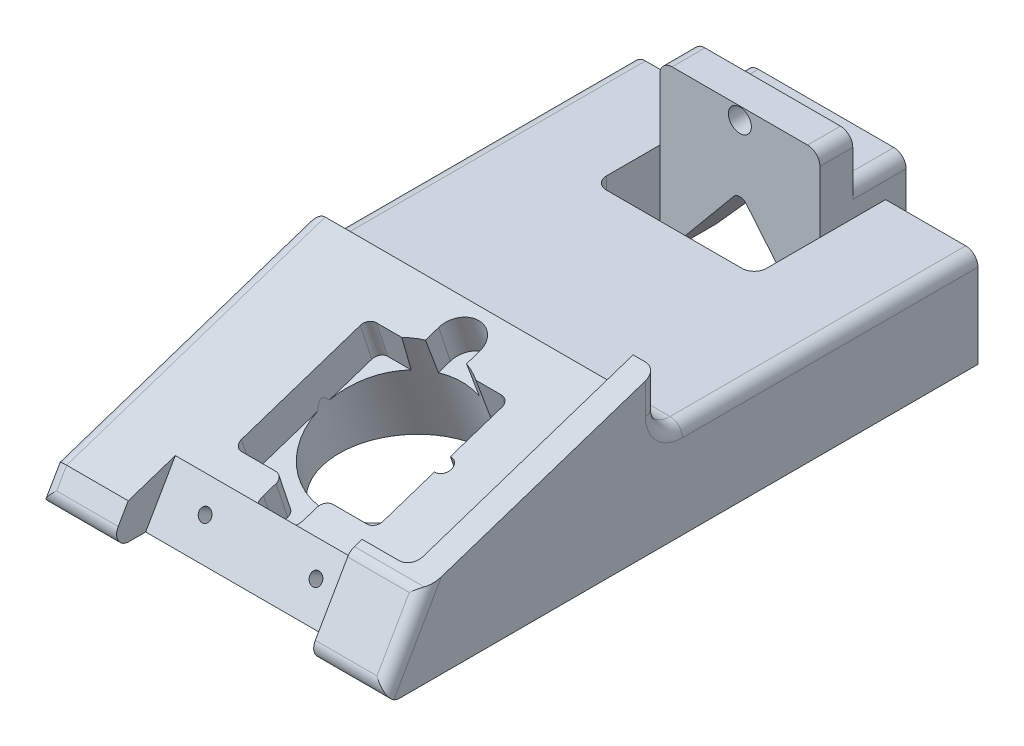
SolidWorks part; units mm, degrees
ref_plane "前视基准面" through (0, 0, 0) normal (0, 0, 1) x (1, 0, 0)
ref_plane "上视基准面" through (0, 0, 0) normal (0, 1, 0) x (1, 0, 0)
ref_plane "右视基准面" through (0, 0, 0) normal (1, 0, 0) x (0, 0, -1)
sketch "草图1" plane through (0, 0, 0) normal (0, 1, 0) x (1, 0, 0)
  line L1 (-21, 36.5) -> (21, 36.5)
  line L2 (-21, 36.5) -> (-21, -36.5)
  line L3 (-21, -36.5) -> (21, -36.5)
  line L4 (21, 36.5) -> (21, -36.5)
  line L5 (-21, 36.5) -> (21, -36.5) construction
  line L6 (-21, -36.5) -> (21, 36.5) construction
  point P0 (0, 0)
  dimension "D1" = 73
  dimension "D2" = 42
extrude "凸台-拉伸1" add sketch "草图1" along normal blind 19
sketch "草图3" plane through (-21, 0, 0) normal (-1, 0, 0) x (0, 0, 1)
  line L0 (-36.5, 11.75) -> (2.5, 11.75)
  line L1 (-36.5, 19) -> (-36.5, 0) construction
  line L2 (-36.5, 0) -> (36.5, 0) construction
  line L3 (2.5, 11.75) -> (2.5, 19)
  line L4 (-36.5, 19) -> (36.5, 19) construction
  line L5 (2.5, 19) -> (30.9777, 9.5649)
  line L6 (30.9777, 9.5649) -> (36.5, 0)
  line L7 (-36.5, 11.75) -> (-36.5, 19)
  line L8 (-36.5, 19) -> (2.5, 19)
  line L9 (36.5, 19) -> (36.5, 0)
  line M5 (36.5, 0) -> (36.5, 19)
  line M6 (36.5, 19) -> (-36.5, 19)
  line M7 (-36.5, 19) -> (-36.5, 0)
  dimension "D1" = 11.75
  dimension "D2" = 39
  dimension "D3" = 60
  dimension "D4" = 30
extrude "切除-拉伸1" cut sketch "草图3" against normal up to next contours L0 L3 M6 M7 | L5 L6 M5 M6
sketch "草图4" plane through (0, 11.75, 0) normal (0, 1, 0) x (1, 0, 0)
  line L0 (21, 36.5) -> (-21, 36.5) construction
  line L2 (-9.75, 28.5) -> (9.75, 28.5)
  line L3 (9.75, 28.5) -> (9.75, 22)
  line L4 (8.25, 20.5) -> (-8.25, 20.5)
  line L5 (-9.75, 22) -> (-9.75, 28.5)
  line L6 (21, -2.5) -> (21, 36.5) construction
  line L7 (-21, 36.5) -> (-21, -2.5) construction
  arc A0 (9.75, 22) -> (8.25, 20.5) centre (8.25, 22) cw
  arc A1 (-8.25, 20.5) -> (-9.75, 22) centre (-8.25, 22) cw
  point P5 (-0.2557, 36.5)
  point P11 (9.75, 20.5)
  dimension "D4" = 1.5
  dimension "D1" = 8
  dimension "D3" = 8
  dimension "D5" = 11.25
  dimension "D6" = 19.5
  dimension "D7" = 11.25
  dimension "D8" = 42
extrude "切除-拉伸2" cut sketch "草图4" against normal blind 19 contours A1 L4 A0 L3 L2 L5
sketch "草图5" plane through (0, 11.75, 0) normal (0, 1, 0) x (1, 0, 0)
  line L0 (9.75, 28.5) -> (9.75, 32.5)
  line L1 (9.75, 32.5) -> (-9.75, 32.5)
  line L2 (-9.75, 32.5) -> (-9.75, 28.5)
  line L7 (-9.75, 28.5) -> (-9.75, 22)
  line L8 (9.75, 28.5) -> (-9.75, 28.5)
  line L9 (9.75, 22) -> (9.75, 28.5)
  line L10 (-8.25, 20.5) -> (8.25, 20.5)
  line L12 (9.75, 28.5) -> (-9.75, 28.5)
  arc A2 (-9.75, 22) -> (-8.25, 20.5) centre (-8.25, 22) ccw
  arc A3 (8.25, 20.5) -> (9.75, 22) centre (8.25, 22) ccw
  dimension "D1" = 4
  dimension "D2" = 0
extrude "凸台-拉伸2" add sketch "草图5" along normal blind 9
sketch "草图6" plane through (0, 11.75, 0) normal (0, 1, 0) x (1, 0, 0)
  line L0 (-9.75, 32.5) -> (-9.75, 39)
  line L1 (-9.75, 39) -> (9.75, 39)
  line L2 (9.75, 39) -> (9.75, 32.5)
  line L3 (9.75, 32.5) -> (-9.75, 32.5)
  dimension "D1" = 6.5
extrude "凸台-拉伸3" add sketch "草图6" against normal up to surface (11.75 mm away) and the other way blind 3.5 up to face at (0, 0, 0)
sketch "草图7" plane through (0, 0, -39) normal (0, 0, -1) x (-1, 0, 0)
  line L0 (-21, 11.75) -> (21, 11.75) construction
  line L1 (-21, 11.75) -> (21, 11.75)
  line L2 (0, 11.75) -> (-9.75, 0)
  line L3 (0, 11.75) -> (9.75, 0)
  line L4 (9.75, 0) -> (-9.75, 0)
  line M2 (-9.75, 0) -> (9.75, 0)
extrude "切除-拉伸3" cut sketch "草图7" against normal up to next contours L3 L2 M2
fillet "圆角1" radius 1.5 4 edges at (-9.75, 15.25, -35.75) (9.75, 15.25, -35.75) (-9.75, 20.75, -30.5) (9.75, 20.75, -30.5)
fillet "圆角2" radius 1 1 edges at (0, 11.75, -33.75)
sketch "草图8" plane through (9.75, 0, 0) normal (1, 0, 0) x (0, 0, -1)
  line L0 (36.5, 0) -> (39, 4)
  line L1 (39, 13.75) -> (39, 0) construction
  line L2 (39, 4) -> (39, 0)
  line L3 (39, 0) -> (36.5, 0)
  dimension "D1" = 4
extrude "切除-拉伸4" cut sketch "草图8" against normal blind 20
fillet "圆角3" radius 1.5 2 edges at (-8.0904, 2, -37.75) (8.0904, 2, -37.75)
sketch "草图9" plane through (0, 17.867, 5.9196) normal (0, 0.9493, 0.3145) x (1, 0, 0)
  line L0 (-18, -24.8476) -> (-21, -24.8476)
  line L1 (-18, 3.6024) -> (18, 3.6024)
  line L2 (-18, 3.6024) -> (-18, -24.8476)
  line L3 (-18, -24.8476) -> (18, -24.8476)
  line L4 (21, -26.3976) -> (21, 3.6024)
  line L5 (21, 3.6024) -> (-21, 3.6024)
  line L6 (-21, 3.6024) -> (-21, -26.3976)
  line L7 (-21, -26.3976) -> (21, -26.3976)
  line L8 (21, -26.3976) -> (21, 3.6024)
  line L9 (21, 3.6024) -> (-21, 3.6024)
  line L10 (-21, 3.6024) -> (-21, -26.3976)
  line L11 (-21, -26.3976) -> (21, -26.3976)
  line L12 (18, 3.6024) -> (18, -24.8476)
  line L13 (-18, 3.6024) -> (18, -24.8476) construction
  line L14 (-18, -24.8476) -> (18, 3.6024) construction
  line L15 (-18, -24.8476) -> (-18, -26.3976)
  point P2 (0, -10.6226)
  line M10 (21, 3.6024) -> (-21, 3.6024)
  line M11 (-21, 3.6024) -> (-21, -26.3976)
  dimension "D2" = 3
  dimension "D3" = 0
  dimension "D4" = 3
  dimension "D5" = 1.55
  dimension "D1" = 0
extrude "切除-拉伸5" cut sketch "草图9" against normal blind 4 contours L12 L2 L3 M10 | L2 L0 M10 M11
sketch "草图10" plane through (0, 15.805, 27.375) normal (0, 0.5, 0.866) x (1, 0, 0)
  line L0 (-12, -18.25) -> (-12, -7.2054)
  line L1 (12, -18.25) -> (12, -7.2054)
  line L2 (-21, -6.0475) -> (18, -6.0475) construction
  line L3 (-21, -6.0475) -> (18, -6.0475)
  line L4 (21, -18.25) -> (21, -7.2054)
  line L5 (21, -7.2054) -> (-21, -7.2054)
  line L6 (-21, -7.2054) -> (-21, -18.25)
  line L7 (-21, -18.25) -> (21, -18.25)
  line L8 (21, -18.25) -> (21, -7.2054)
  line L9 (21, -7.2054) -> (-21, -7.2054)
  line L10 (-21, -7.2054) -> (-21, -18.25)
  line L11 (-21, -18.25) -> (21, -18.25)
  line L12 (-12, -7.2054) -> (-12, -6.0475)
  line L13 (12, -7.2054) -> (12, -6.0475)
  line L14 (12, -6.0475) -> (-12, -6.0475)
  line M8 (21, -7.2054) -> (-21, -7.2054)
  line M10 (-21, -18.25) -> (21, -18.25)
  dimension "D2" = 9
  dimension "D3" = 9
  dimension "D1" = 0
extrude "切除-拉伸7" cut sketch "草图10" against normal up to vertex (12.8767 mm away) contours L1 L0 M10 M8 | L13 L3 L12 M8
sketch "草图12" plane through (0, 14.07, 4.6616) normal (0, 0.9493, 0.3145) x (1, 0, 0)
  line L0 (-17.249, 2.2772) -> (18, -24.8476) construction
  line L6 (18, 2.2772) -> (-21, 2.2772)
  line L7 (-21, 2.2772) -> (-21, -24.8476)
  line L8 (-21, -24.8476) -> (-12, -24.8476)
  line L9 (-12, -24.8476) -> (12, -24.8476)
  line L10 (12, -24.8476) -> (18, -24.8476)
  line L11 (18, -24.8476) -> (18, 2.2772)
  line L12 (18, 2.2772) -> (-21, 2.2772)
  line L13 (-21, 2.2772) -> (-21, -24.8476)
  line L14 (-21, -24.8476) -> (-12, -24.8476)
  line L15 (-12, -24.8476) -> (12, -24.8476)
  line L16 (12, -24.8476) -> (18, -24.8476)
  line L17 (18, -24.8476) -> (18, 2.2772)
  circle A0 centre (0.3755, -11.2852) radius 8.5
  dimension "D2" = 17
  dimension "D1" = 0
sketch "草图13" plane through (0, 14.07, 4.6616) normal (0, 0.9493, 0.3145) x (1, 0, 0)
  line L0 (9.0005, -12.7026) -> (10.0709, -12.7026) construction
  line L1 (-8.2495, -4.0776) -> (9.0005, -4.0776)
  line L2 (-8.2495, -4.0776) -> (-8.2495, -21.3276)
  line L3 (-8.2495, -21.3276) -> (9.0005, -21.3276)
  line L4 (9.0005, -4.0776) -> (9.0005, -21.3276)
  line L5 (-8.2495, -4.0776) -> (9.0005, -21.3276) construction
  line L6 (-8.2495, -21.3276) -> (9.0005, -4.0776) construction
  line L7 (10.0709, -12.7276) -> (10.0709, -12.6776)
  line L8 (9.0709, -13.7276) -> (8.8135, -13.7276)
  line L9 (9.0709, -11.6776) -> (8.8135, -11.6776)
  line L10 (0.3755, -21.3276) -> (0.3755, -23.9461) construction
  line L11 (-2.1245, -23.9461) -> (2.8755, -23.9461) construction
  line L12 (-2.1245, -23.9461) -> (-2.1245, -20.9461)
  line L13 (2.8755, -23.9461) -> (2.8755, -20.9461)
  line L14 (-999.6245, -12.7026) -> (49000.3755, -12.7026) construction
  line L15 (2.8755, -1.459) -> (2.8755, -4.459)
  line L16 (-2.1245, -1.459) -> (-2.1245, -4.459)
  arc A2 (10.0709, -12.7276) -> (9.0709, -13.7276) centre (9.0709, -12.7276) cw
  arc A3 (10.0709, -12.6776) -> (9.0709, -11.6776) centre (9.0709, -12.6776) ccw
  circle A4 centre (0.3755, -23.9461) radius 2.5
  circle A5 centre (0.3755, -1.459) radius 2.5
  point P12 (10.0709, -12.7026)
  point P23 (0.3755, -23.9461)
  dimension "D2" = 1
  dimension "D1" = 17.25
  dimension "D3" = 17.25
  dimension "D4" = 3
  dimension "D5" = 5
extrude "切除-拉伸11" cut sketch "草图13" against normal blind 4.5
extrude "切除-拉伸12" cut sketch "草图12" against normal up to next draft 2 contours L0 A0 | A0 L0 draft outward yes
sketch "草图16" plane through (0, 14.07, 4.6616) normal (0, 0.9493, 0.3145) x (1, 0, 0)
  line L0 (9.0709, -13.7276) -> (8.8135, -13.7276) construction
  line L1 (9.0709, -11.6776) -> (8.8135, -11.6776) construction
  line L2 (9.0709, -13.7276) -> (8.8135, -13.7276)
  line L3 (9.0709, -11.6776) -> (8.8135, -11.6776)
  line L4 (8.8135, -11.6776) -> (8.8135, -13.7276)
  line L5 (9.0709, -11.6776) -> (9.0709, -13.7276)
  line L6 (10.0709, -12.6776) -> (10.0709, -12.7276)
  arc A0 (9.0709, -13.7276) -> (10.0709, -12.7276) centre (9.0709, -12.7276) ccw construction
  arc A1 (10.0709, -12.6776) -> (9.0709, -11.6776) centre (9.0709, -12.6776) ccw construction
  arc A2 (9.0709, -13.7276) -> (10.0709, -12.7276) centre (9.0709, -12.7276) ccw
  arc A3 (10.0709, -12.6776) -> (9.0709, -11.6776) centre (9.0709, -12.6776) ccw
  line M8 (9.0005, -4.0776) -> (9.0005, -21.3276)
  line M9 (9.0005, -4.0776) -> (9.0005, -21.3276)
extrude "切除-拉伸14" cut sketch "草图16" against normal through all contours L6 A3 L5 A2 | L5 L3 L2 M8 M9
sketch "草图17" plane through (0, 0, -28.5) normal (0, 0, -1) x (-1, 0, 0)
  line L0 (-9.75, 19.25) -> (9.75, 19.25)
  line L1 (-8.25, 20.75) -> (8.25, 20.75) construction
  circle A0 centre (0, 19.25) radius 1.4
  dimension "D1" = 2.8
  dimension "D2" = 1.5
extrude "切除-拉伸15" cut sketch "草图17" along normal blind 2 contours A0 L0 | A0 L0
sketch "草图18" plane through (0, 0, -30.5) normal (0, 0, 1) x (1, 0, 0)
  circle A0 centre (0, 19.25) radius 0.75
  circle A1 centre (0, 19.25) radius 1.4 construction
  circle A2 centre (0, 19.25) radius 1.4
  dimension "D2" = 1.5
  dimension "D1" = 0
extrude "切除-拉伸16" cut sketch "草图18" against normal blind 4 contours A0
sketch "草图19" plane through (0, 13.7957, 23.8949) normal (0, 0.5, 0.866) x (1, 0, 0)
  line L0 (-1012, -11.9569) -> (1012, -11.9569) construction
  line L2 (-12, -8.7069) -> (-1.9563, -8.7069) construction
  circle A0 centre (-6.75, -11.9569) radius 0.75
  circle A1 centre (6.75, -11.9569) radius 0.75
  dimension "D2" = 1.5
  dimension "D3" = 1.5
  dimension "D1" = 3.25
  dimension "D4" = 13.5
extrude "切除-拉伸17" cut sketch "草图19" against normal blind 3
sketch "草图20" plane through (0, 0, -36.5) normal (0, 0, -1) x (-1, 0, 0)
  line L0 (-21, 11.75) -> (-9.75, 11.75) construction
  line L1 (-21, 11.75) -> (-21, 0) construction
  circle A0 centre (-15.25, 6) radius 0.75
  dimension "D3" = 1.5
  dimension "D1" = 5.75
  dimension "D2" = 5.75
extrude "切除-拉伸18" cut sketch "草图20" against normal blind 4 draft 5
mirror "镜向1" about plane through (0, 0, 0) normal (1, 0, 0) of "切除-拉伸18"
fillet "圆角4" radius 1.5 2 edges at (16.5, 0, 36.5) (-16.5, 0, 36.5)
fillet "圆角5" radius 1.5 4 edges at (16.5, 9.5649, 30.9777) (-16.5, 9.5649, 30.9777) (21, 5.9075, 33.0893) (-21, 5.9075, 33.0893)
fillet "圆角6" radius 3 1 edges at (0, 11.75, 2.5)
fillet "圆角7" radius 1.5 6 edges at (21, 11.75, -18.5) (21, 12.6287, 1.6213) (-21, 11.75, -18.5) (-21, 12.6287, 1.6213) (21, 16.875, 2.5) (-21, 10.5208, 15.3742)
fillet "圆角8" radius 1.5 5 edges at (-21, 7.1436, 28.5426) (18, 8.1539, 28.8773) (-20.7539, 9.8851, 30.0114) (-20.981, 9.7579, 29.4088) (-20.5607, 5.8383, 28.1102)
fillet "圆角9" radius 1 6 edges at (2.8755, 5.2266, 24.1993) (-2.1245, 5.2266, 24.1993) (-8.2495, 10.6518, 7.8246) (9.0005, 10.6518, 7.8246) (-8.2495, 5.2266, 24.1993) (9.0005, 5.2266, 24.1993)
sketch "草图21" plane through (0, -7.8146, 23.5867) normal (0, 0.3145, -0.9493) x (-1, 0, 0)
  line L3 (21, 13.3221) -> (21, 16.8586)
  line L4 (12, 14.8221) -> (19.5, 14.8221)
  line L5 (19.5, 14.8221) -> (19.5, 18.8221)
  line L6 (19.5, 18.8221) -> (12, 18.8221)
  line L7 (12, 18.8221) -> (12, 14.8221)
  line L8 (12, 14.8221) -> (19.5, 14.8221)
  line L9 (19.5, 14.8221) -> (19.5, 18.8221)
  line L10 (19.5, 18.8221) -> (12, 18.8221)
  line L11 (12, 18.8221) -> (12, 14.8221)
  line L12 (20.714, 18.8221) -> (19.5, 18.8221)
  line L13 (19.5, 18.8221) -> (19.5, 14.8221)
  line L14 (21, 13.3221) -> (21, 16.8586)
  line L15 (20.714, 18.8221) -> (19.5, 18.8221)
  line L16 (19.5, 18.8221) -> (19.5, 14.8221)
  arc A1 (21, 13.3221) -> (19.5, 14.8221) centre (19.5, 13.3221) ccw
  arc A2 (21, 13.3221) -> (19.5, 14.8221) centre (19.5, 13.3221) ccw
  ellipse E1 centre (19.5, 16.8586) end of major axis (19.5, 13.5155) minor radius 1.5 (21, 16.8586) -> (20.714, 18.8221) ccw
  ellipse E2 centre (19.5, 16.8586) end of major axis (19.5, 13.5155) minor radius 1.5 (21, 16.8586) -> (20.714, 18.8221) ccw
  line M5 (12, 14.8221) -> (19.5, 14.8221)
  line M6 (19.5, 14.8221) -> (19.5, 18.8221)
  line M7 (19.5, 18.8221) -> (12, 18.8221)
  line M8 (12, 18.8221) -> (12, 14.8221)
  dimension "D1" = 0
  dimension "D2" = 0
extrude "切除-拉伸19" cut sketch "草图21" against normal blind 10 contours M8 M5 M6 M7 | L14 E2 L15 A2 M6
